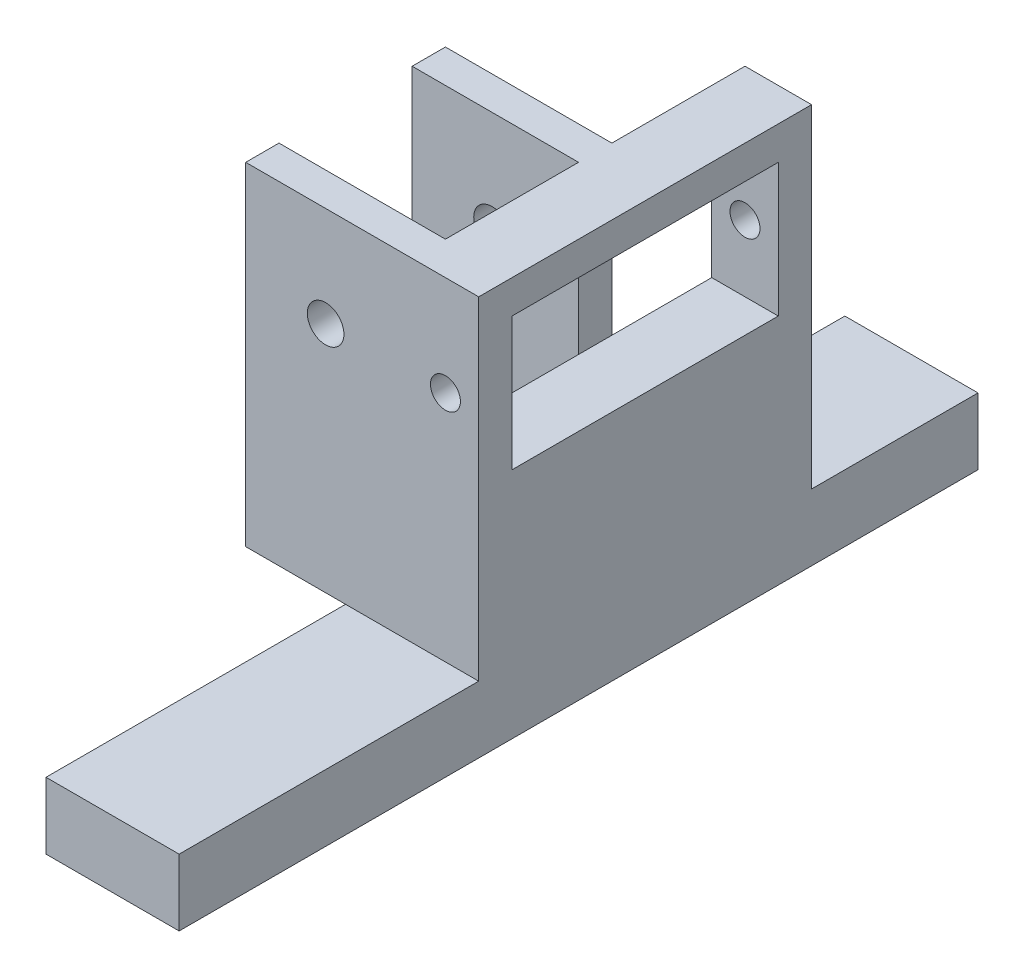
SolidWorks part; units mm, degrees
ref_plane "Front Plane" through (0, 0, 0) normal (0, 0, 1) x (1, 0, 0)
ref_plane "Top Plane" through (0, 0, 0) normal (0, 1, 0) x (1, 0, 0)
ref_plane "Right Plane" through (0, 0, 0) normal (1, 0, 0) x (0, 0, -1)
sketch "Sketch4" plane through (0, 0, 0) normal (0, 1, 0) x (1, 0, 0)
  line L1 (0, 0) -> (40, 0)
  line L2 (0, 0) -> (0, 80)
  line L3 (0, 80) -> (40, 80)
  line L4 (40, 0) -> (40, 80)
  dimension "D1" = 80
  dimension "D2" = 40
extrude "Boss-Extrude4" add sketch "Sketch4" along normal blind 5
sketch "Sketch5" plane through (0, 5, 0) normal (0, 1, 0) x (1, 0, 0)
  line L0 (40, 40) -> (30, 40)
  line L1 (30, 30) -> (30, 50) construction
  line L2 (40, 50) -> (30, 50)
  line L3 (30, 50) -> (30, 55)
  line L4 (0, 80) -> (0, 0)
  line L5 (0, 0) -> (40, 0)
  line L6 (40, 0) -> (40, 80)
  line L7 (40, 80) -> (0, 80)
  line L8 (0, 80) -> (0, 0)
  line L9 (0, 0) -> (40, 0)
  line L10 (40, 0) -> (40, 80)
  line L11 (40, 80) -> (0, 80)
  line L12 (30, 55) -> (40, 55)
  line L13 (40, 55) -> (40, 50)
  line L14 (40, 30) -> (30, 30)
  line L15 (30, 30) -> (30, 25)
  line L16 (30, 25) -> (40, 25)
  line L17 (40, 25) -> (40, 30)
  point P9 (30, 40)
  line M11 (40, 0) -> (40, 80)
  dimension "D2" = 10
  dimension "D3" = 10
  dimension "D4" = 5
  dimension "D5" = 5
  dimension "D1" = 0
extrude "Boss-Extrude6" add sketch "Sketch5" along normal blind 50 contours L12 L3 L2 M11 | L15 L16 L10 L14 region at (35, 5, -52.5) region at (35, 5, -27.5)
sketch "Sketch7" plane through (0, 0, -50) normal (0, 0, 1) x (1, 0, 0)
  line L1 (30, 5) -> (40, 5)
  line L2 (30, 5) -> (30, 30)
  line L3 (30, 30) -> (40, 30)
  line L4 (40, 5) -> (40, 30)
  line L5 (40, 55) -> (40, 5) construction
  line L7 (30, 55) -> (40, 55)
  line L8 (30, 55) -> (30, 50)
  line L9 (30, 50) -> (40, 50)
  line L10 (40, 55) -> (40, 50)
  dimension "D1" = 25
  dimension "D2" = 10
  dimension "D3" = 5
extrude "Boss-Extrude7" add sketch "Sketch7" along normal up to surface (20 mm away) contours L8 L7 L10 L9 | L2 L1 L4 L3 up to face at (35, 30, -30)
sketch "Sketch9" plane through (0, 0, 0) normal (-1, 0, 0) x (0, 0, 1)
  line L4 (-80, 0) -> (0, 0)
  line L5 (0, 0) -> (0, 5)
  line L6 (0, 5) -> (-80, 5)
  line L7 (-80, 5) -> (-80, 0)
  line L8 (-80, 0) -> (0, 0)
  line L9 (0, 0) -> (0, 5)
  line L10 (0, 5) -> (-80, 5)
  line L12 (-80, 5) -> (-80, 0)
  dimension "D1" = 0
extrude "Boss-Extrude9" add sketch "Sketch9" along normal blind 10
sketch "Sketch10" plane through (0, 0, 0) normal (0, 0, 1) x (1, 0, 0)
  line L4 (-10, 0) -> (40, 0)
  line L5 (40, 0) -> (40, 5)
  line L6 (40, 5) -> (-10, 5)
  line L7 (-10, 5) -> (-10, 0)
  line L8 (-10, 0) -> (40, 0)
  line L9 (40, 0) -> (40, 5)
  line L10 (40, 5) -> (-10, 5)
  line L11 (-10, 5) -> (-10, 0)
  dimension "D1" = 0
extrude "Boss-Extrude10" add sketch "Sketch10" along normal blind 20
sketch "Sketch11" plane through (0, 0, -50) normal (0, 0, 1) x (1, 0, 0)
  line L0 (30, 40) -> (35, 40)
  line L4 (30, 30) -> (40, 30)
  line L5 (40, 30) -> (40, 50)
  line L6 (40, 50) -> (30, 50)
  line L7 (30, 50) -> (30, 30)
  line L8 (30, 30) -> (40, 30)
  line L9 (40, 30) -> (40, 50)
  line L10 (40, 50) -> (30, 50)
  line L11 (30, 50) -> (30, 30)
  circle A0 centre (35, 40) radius 2.25
  dimension "D3" = 4.5
  dimension "D2" = 5
  dimension "D1" = 0
extrude "Cut-Extrude1" cut sketch "Sketch11" against normal mid plane 50 contours A0 region at (35, 42.1864, -50)
sketch "Sketch12" plane through (0, 0, -25) normal (0, 0, 1) x (1, 0, 0)
  circle A0 centre (35, 40) radius 2.25 construction
  circle A1 centre (35, 40) radius 2.25
  circle A2 centre (35, 40) radius 4
  dimension "D1" = 8
extrude "Cut-Extrude2" cut sketch "Sketch12" against normal blind 2
sketch "Sketch15" plane through (30, 0, 0) normal (-1, 0, 0) x (0, 0, 1)
  line L1 (-55, 55) -> (-50, 55)
  line L2 (-55, 55) -> (-55, 5)
  line L3 (-55, 5) -> (-50, 5)
  line L4 (-50, 55) -> (-50, 5)
  line L5 (-25, 55) -> (-30, 55)
  line L6 (-25, 55) -> (-25, 5)
  line L7 (-25, 5) -> (-30, 5)
  line L8 (-30, 55) -> (-30, 5)
  dimension "D1" = 50
  dimension "D2" = 5
  dimension "D3" = 50
  dimension "D4" = 5
extrude "Boss-Extrude11" add sketch "Sketch15" along normal blind 20
sketch "Sketch16" plane through (0, 0, -25) normal (0, 0, 1) x (1, 0, 0)
  line L0 (35, 40) -> (17, 40)
  circle A0 centre (35, 40) radius 4 construction
  circle A1 centre (35, 40) radius 4
  circle A2 centre (17, 40) radius 2.75
  dimension "D2" = 5.5
  dimension "D1" = 18
extrude "Cut-Extrude4" cut sketch "Sketch16" against normal up to surface (30 mm away) contours A2 region at (14.3278, 40, -25) up to face at (32.75, 40, -55)
sketch "Sketch19" plane through (10, 0, 0) normal (-1, 0, 0) x (0, 0, 1)
  line L4 (-55, 55) -> (-55, 5)
  line L5 (-55, 5) -> (-50, 5)
  line L6 (-50, 5) -> (-50, 55)
  line L7 (-50, 55) -> (-55, 55)
  line L8 (-55, 55) -> (-55, 5)
  line L10 (-50, 5) -> (-50, 55)
  line L11 (-50, 55) -> (-55, 55)
  line L12 (-25, 5) -> (-25, 55)
  line L13 (-25, 55) -> (-30, 55)
  line L14 (-30, 55) -> (-30, 5)
  line L15 (-30, 5) -> (-25, 5)
  line L16 (-25, 5) -> (-25, 55)
  line L17 (-25, 55) -> (-30, 55)
  line L18 (-30, 55) -> (-30, 5)
  line L20 (-55, 5) -> (-50, 5)
  line L21 (-30, 5) -> (-25, 5)
  dimension "D1" = 0
  dimension "D2" = 0
extrude "Boss-Extrude12" add sketch "Sketch19" along normal blind 5
sketch "Sketch21" plane through (0, 0, 0) normal (0, -1, 0) x (1, 0, 0)
  line L4 (40, -80) -> (40, 20)
  line L5 (40, 20) -> (-10, 20)
  line L6 (-10, 20) -> (-10, -80)
  line L7 (-10, -80) -> (40, -80)
  line L8 (40, -80) -> (40, 20)
  line L9 (40, 20) -> (-10, 20)
  line L10 (-10, 20) -> (-10, -80)
  line L11 (-10, -80) -> (40, -80)
  dimension "D1" = 0
extrude "Boss-Extrude14" add sketch "Sketch21" along normal blind 5
sketch "Sketch22" plane through (0, 0, -80) normal (0, 0, -1) x (-1, 0, 0)
  line L4 (-40, 5) -> (-40, -5)
  line L5 (-40, -5) -> (10, -5)
  line L6 (10, -5) -> (10, 5)
  line L7 (10, 5) -> (-40, 5)
  line L8 (-40, 5) -> (-40, -5)
  line L9 (-40, -5) -> (10, -5)
  line L10 (10, -5) -> (10, 5)
  line L11 (10, 5) -> (-40, 5)
  dimension "D1" = 0
extrude "Boss-Extrude15" add sketch "Sketch22" along normal blind 20
sketch "Sketch24" plane through (0, 55, 0) normal (0, 1, 0) x (1, 0, 0)
  line L1 (5, 55) -> (40, 55)
  line L2 (5, 55) -> (5, 50)
  line L3 (5, 50) -> (40, 50)
  line L4 (40, 55) -> (40, 50)
  line L5 (40, 25) -> (40, 55) construction
  dimension "D1" = 35
  dimension "D2" = 5
extrude "Cut-Extrude5" cut sketch "Sketch24" against normal blind 50
sketch "Sketch25" plane through (0, 0, -50) normal (0, 0, -1) x (-1, 0, 0)
  line L4 (-30, 5) -> (-30, 30)
  line L5 (-30, 30) -> (-40, 30)
  line L6 (-40, 30) -> (-40, 5)
  line L7 (-40, 5) -> (-30, 5)
  line L8 (-30, 5) -> (-30, 30)
  line L9 (-30, 30) -> (-40, 30)
  line L10 (-40, 30) -> (-40, 5)
  line L11 (-40, 5) -> (-30, 5)
  line L12 (-30, 50) -> (-30, 55)
  line L13 (-30, 55) -> (-40, 55)
  line L14 (-40, 55) -> (-40, 50)
  line L15 (-40, 50) -> (-30, 50)
  line L16 (-30, 50) -> (-30, 55)
  line L17 (-30, 55) -> (-40, 55)
  line L18 (-40, 55) -> (-40, 50)
  line L19 (-40, 50) -> (-30, 50)
  dimension "D1" = 0
  dimension "D2" = 0
extrude "Boss-Extrude16" add sketch "Sketch25" along normal blind 25
sketch "Sketch26" plane through (0, 30, 0) normal (0, 1, 0) x (1, 0, 0)
  line L1 (40, 75) -> (30, 75)
  line L2 (40, 75) -> (40, 70)
  line L3 (40, 70) -> (30, 70)
  line L4 (30, 75) -> (30, 70)
  line L5 (30, 30) -> (30, 75) construction
  dimension "D1" = 5
  dimension "D2" = 10
extrude "Boss-Extrude17" add sketch "Sketch26" along normal blind 20
sketch "Sketch27" plane through (0, 0, -27) normal (0, 0, 1) x (1, 0, 0)
  circle A0 centre (35, 40) radius 2.25 construction
  circle A1 centre (35, 40) radius 4
  circle A2 centre (35, 40) radius 4
  circle A3 centre (35, 40) radius 2.25
  dimension "D1" = 0
extrude "Boss-Extrude18" add sketch "Sketch27" along normal up to surface (2 mm away) up to face at (19.75, 40, -25)
sketch "Sketch28" plane through (0, 0, -25) normal (0, 0, 1) x (1, 0, 0)
  circle A0 centre (35, 40) radius 2.25 construction
  circle A1 centre (35, 40) radius 2.25
extrude "Cut-Extrude6" cut sketch "Sketch28" against normal blind 50
sketch "Sketch29" plane through (0, 5, 0) normal (0, 1, 0) x (1, 0, 0)
  line L0 (5, 30) -> (5, 50) construction
  line L2 (5, 50) -> (30, 50)
  line L3 (5, 50) -> (5, 55)
  line L4 (5, 55) -> (30, 55)
  line L5 (30, 50) -> (30, 55)
  line L6 (30, 30) -> (30, 75) construction
  dimension "D1" = 20
  dimension "D2" = 5
  dimension "D3" = 25
extrude "Boss-Extrude19" add sketch "Sketch29" along normal up to surface (50 mm away) contours L3 L2 L5 L4 up to face at (25, 55, -43.3333)
sketch "Sketch31" plane through (0, 0, -25) normal (0, 0, 1) x (1, 0, 0)
  circle A0 centre (17, 40) radius 2.75 construction
  circle A1 centre (17, 40) radius 2.75
extrude "Cut-Extrude7" cut sketch "Sketch31" against normal blind 30
sketch "Sketch32" plane through (0, 5, 0) normal (0, 1, 0) x (1, 0, 0)
  line L0 (-10, 100) -> (40, 100) construction
  line L1 (20, 100) -> (-10, 100)
  line L2 (20, 100) -> (20, 55)
  line L3 (20, 55) -> (-10, 55)
  line L4 (-10, 100) -> (-10, 55)
  line L5 (20, 530) -> (20, -20) construction
  line L6 (-10, -20) -> (-10, 100) construction
  line L7 (5, 25) -> (40, 25) construction
  line L8 (-10, -20) -> (20, -20)
  line L9 (-10, -20) -> (-10, 25)
  line L10 (-10, 25) -> (20, 25)
  line L11 (20, -20) -> (20, 25)
  dimension "D1" = 45
  dimension "D2" = 30
extrude "Cut-Extrude8" cut sketch "Sketch32" against normal blind 10
sketch "Sketch33" plane through (-10, 0, 0) normal (-1, 0, 0) x (0, 0, 1)
  line L4 (-55, 5) -> (-55, -5)
  line L5 (-55, -5) -> (-25, -5)
  line L6 (-25, -5) -> (-25, 5)
  line L7 (-25, 5) -> (-55, 5)
  line L8 (-55, 5) -> (-55, -5)
  line L9 (-55, -5) -> (-25, -5)
  line L10 (-25, -5) -> (-25, 5)
  line L11 (-25, 5) -> (-55, 5)
  dimension "D1" = 0
extrude "Cut-Extrude9" cut sketch "Sketch33" against normal up to surface (30 mm away) up to face at (20, 0, -2.5)
